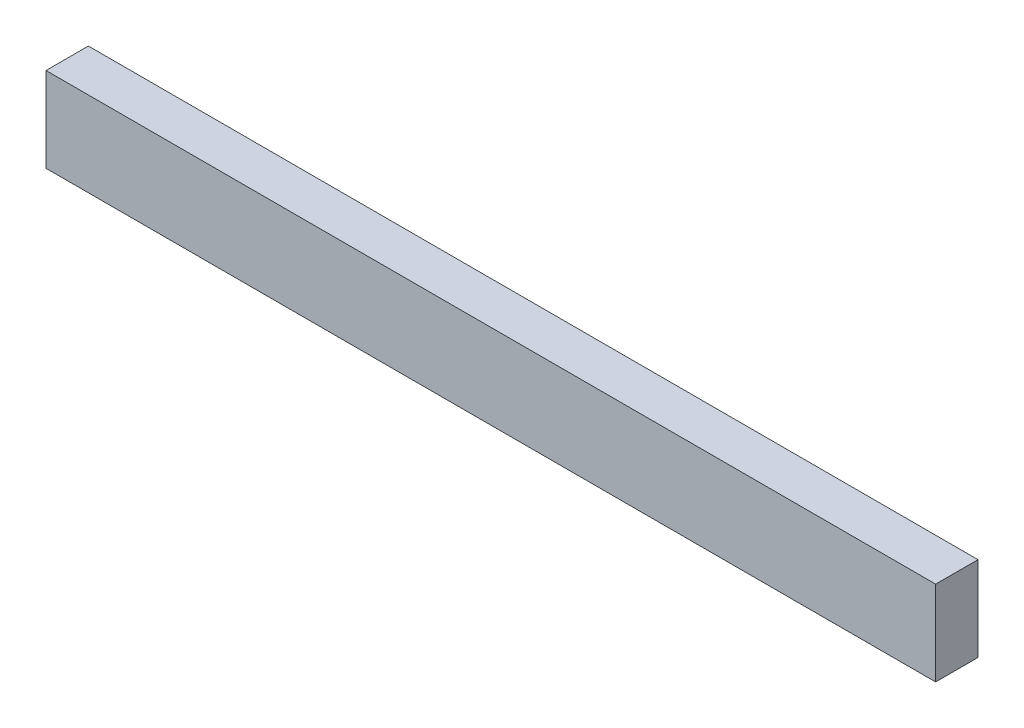
SolidWorks part; units mm, degrees
ref_plane "Front Plane" through (0, 0, 0) normal (0, 0, 1) x (1, 0, 0)
ref_plane "Top Plane" through (0, 0, 0) normal (0, 1, 0) x (1, 0, 0)
ref_plane "Right Plane" through (0, 0, 0) normal (1, 0, 0) x (0, 0, -1)
sketch "Sketch1" plane through (0, 0, 0) normal (0, 0, 1) x (1, 0, 0)
  line L1 (0, 0) -> (533.4, 0)
  line L2 (0, 0) -> (0, 50.8)
  line L3 (0, 50.8) -> (533.4, 50.8)
  line L4 (533.4, 0) -> (533.4, 50.8)
  dimension "D1" = 50.8
  dimension "D2" = 533.4
extrude "Boss-Extrude1" add sketch "Sketch1" along normal blind 25.4
